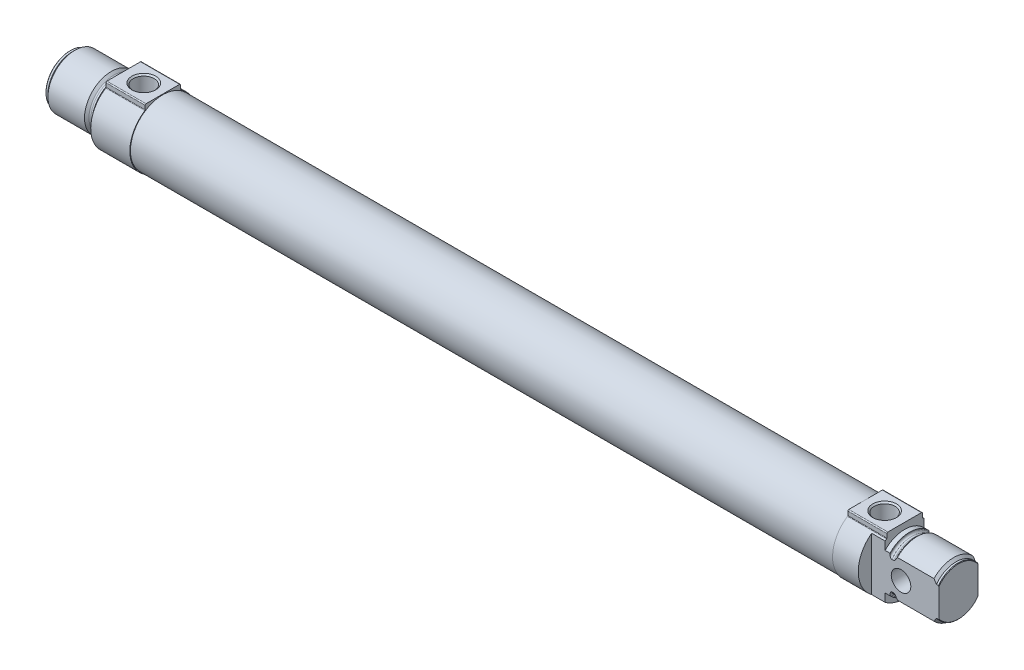
SolidWorks part; units mm, degrees
ref_plane "Ebene vorne" through (0, 0, 0) normal (0, 0, 1) x (1, 0, 0)
ref_plane "Ebene oben" through (0, 0, 0) normal (0, 1, 0) x (1, 0, 0)
ref_plane "Ebene rechts" through (0, 0, 0) normal (1, 0, 0) x (0, 0, -1)
sketch "Skizze1" plane through (0, 0, 0) normal (0, 0, 1) x (1, 0, 0)
  line L0 (0, 0) -> (0, 9.8)
  line L1 (0, 9.8) -> (0.2, 10)
  line L2 (0.2, 10) -> (1, 10)
  line L3 (1, 10) -> (2, 11)
  line L4 (2, 11) -> (16.95, 11)
  line L5 (16.95, 11) -> (17.8657, 10.0843)
  line L6 (18.4314, 9.85) -> (19.2, 9.85)
  line L7 (20, 10.65) -> (20, 11)
  line L8 (20, 11) -> (22, 11)
  line L9 (22, 11) -> (22, 0)
  line L10 (22, 0) -> (0, 0)
  line L11 (22, 0) -> (0, 0) construction
  arc A0 (17.8657, 10.0843) -> (18.4314, 9.85) centre (18.4314, 10.65) ccw
  arc A1 (19.2, 9.85) -> (20, 10.65) centre (19.2, 10.65) ccw
revolve "Rotation1" add sketch "Skizze1" angle 360 about L11 reverse direction yes
cosmetic thread "Gewindedarstellung1" parameters "D1"=15.87, "D2"=20.16
ref_plane "Ebene1" through (31.8, 0, 0) normal (1, 0, 0) x (0, 0, -1)
ref_plane "Ebene2" through (10.5, 0, 0) normal (1, 0, 0) x (0, 0, -1)
ref_plane "Ebene3" through (0, -16, 0) normal (0, 1, 0) x (1, 0, 0)
ref_plane "Ebene4" through (0, 14.9, 0) normal (0, 1, 0) x (1, 0, 0)
ref_plane "Ebene5" through (0, 0, 0) normal (0, 1, 0) x (1, 0, 0)
ref_plane "Ebene6" through (0, 0, 0) normal (0, 1, 0) x (1, 0, 0)
ref_plane "Ebene7" through (22, 0, 0) normal (1, 0, 0) x (0, 0, -1)
ref_plane "Ebene8" through (22, 0, 0) normal (1, 0, 0) x (0, 0, -1)
ref_plane "Ebene9" through (35, 0, 0) normal (1, 0, 0) x (0, 0, -1)
ref_plane "Ebene10" through (26.5, 0, 0) normal (1, 0, 0) x (0, 0, -1)
ref_plane "Ebene11" through (46.5, 0, 0) normal (1, 0, 0) x (0, 0, -1)
sketch "Skizze2" plane through (22, 0, 0) normal (1, 0, 0) x (0, 0, -1)
  line L0 (7.25, 11.5515) -> (7.25, 13.1)
  line L1 (6.85, 13.5) -> (-6.85, 13.5)
  line L2 (-7.25, 13.1) -> (-7.25, 11.5515)
  arc A0 (-7.3859, 11.3004) -> (7.3859, 11.3004) centre (0, 0) ccw
  arc A1 (7.3859, 11.3004) -> (7.25, 11.5515) centre (7.55, 11.5515) cw
  arc A2 (7.25, 13.1) -> (6.85, 13.5) centre (6.85, 13.1) ccw
  arc A3 (-6.85, 13.5) -> (-7.25, 13.1) centre (-6.85, 13.1) ccw
  arc A4 (-7.25, 11.5515) -> (-7.3859, 11.3004) centre (-7.55, 11.5515) cw
extrude "Aufsatz-Linear austragen1" add sketch "Skizze2" along normal blind 16
ref_plane "Ebene12" through (34, 0, 0) normal (1, 0, 0) x (0, 0, -1)
ref_plane "Ebene13" through (0, 0, 0) normal (0, 0, 1) x (1, 0, 0)
ref_plane "Ebene14" through (0, 0, -9.1) normal (0, 0, 1) x (1, 0, 0)
ref_plane "Ebene15" through (0, 0, 0) normal (0, 1, 0) x (1, 0, 0)
ref_plane "Ebene16" through (0, 6.9, 0) normal (0, 1, 0) x (1, 0, 0)
ref_plane "Ebene17" through (0, 0, -6.6) normal (0, 0, 1) x (1, 0, 0)
ref_plane "Ebene18" through (0, 0, 0) normal (0, 1, 0) x (1, 0, 0)
ref_plane "Ebene19" through (0, 6.9, 0) normal (0, 1, 0) x (1, 0, 0)
ref_plane "Ebene20" through (0, 7.8206, -1.379) normal (0, 0.9848, -0.1736) x (1, 0, 0)
ref_plane "Ebene21" through (0, 6.3434, -1.1185) normal (0, 0.9848, -0.1736) x (1, 0, 0)
sketch "Skizze3" plane through (0, 0, 0) normal (0, 0, 1) x (1, 0, 0)
  line L0 (38, 0) -> (38, 13.25)
  line L1 (38, 13.25) -> (325.5, 13.25)
  line L2 (325.5, 13.25) -> (325.5, 0)
  line L3 (325.5, 0) -> (38, 0)
  line L4 (325.5, 0) -> (38, 0) construction
revolve "Rotation2" add sketch "Skizze3" angle 360 about L4 reverse direction yes
ref_plane "Ebene22" through (325.5, 0, 0) normal (1, 0, 0) x (0, 0, -1)
sketch "Skizze4" plane through (325.5, 0, 0) normal (1, 0, 0) x (0, 0, -1)
  line L0 (7.25, 11.5515) -> (7.25, 13.1)
  line L1 (6.85, 13.5) -> (-6.85, 13.5)
  line L2 (-7.25, 13.1) -> (-7.25, 11.5515)
  arc A0 (-7.3859, 11.3004) -> (7.3859, 11.3004) centre (0, 0) ccw
  arc A1 (7.3859, 11.3004) -> (7.25, 11.5515) centre (7.55, 11.5515) cw
  arc A2 (7.25, 13.1) -> (6.85, 13.5) centre (6.85, 13.1) ccw
  arc A3 (-6.85, 13.5) -> (-7.25, 13.1) centre (-6.85, 13.1) ccw
  arc A4 (-7.25, 11.5515) -> (-7.3859, 11.3004) centre (-7.55, 11.5515) cw
extrude "Aufsatz-Linear austragen2" add sketch "Skizze4" along normal blind 16
ref_plane "Ebene23" through (329.3, 0, 0) normal (1, 0, 0) x (0, 0, -1)
ref_plane "Ebene24" through (329.5, 0, 0) normal (1, 0, 0) x (0, 0, -1)
ref_plane "Ebene25" through (0, 0, 6.6) normal (0, 0, 1) x (1, 0, 0)
ref_plane "Ebene26" through (0, 0, 0) normal (0, 1, 0) x (1, 0, 0)
ref_plane "Ebene27" through (0, 6.9, 0) normal (0, 1, 0) x (1, 0, 0)
ref_plane "Ebene28" through (0, 7.8206, 1.379) normal (0, 0.9848, 0.1736) x (1, 0, 0)
ref_plane "Ebene29" through (0, 6.3434, 1.1185) normal (0, 0.9848, 0.1736) x (1, 0, 0)
ref_plane "Ebene30" through (389.5, 0, 0) normal (1, 0, 0) x (0, 0, -1)
sketch "Skizze5" plane through (0, 0, 0) normal (0, 0, 1) x (1, 0, 0)
  line L0 (341.5, 0) -> (341.5, 11)
  line L1 (341.5, 11) -> (343.5, 11)
  line L2 (343.5, 11) -> (343.5, 10.65)
  line L3 (344.3, 9.85) -> (345.0686, 9.85)
  line L4 (345.6343, 10.0843) -> (346.55, 11)
  line L5 (346.55, 11) -> (361.5, 11)
  line L6 (361.5, 11) -> (362.5, 10)
  line L7 (362.5, 10) -> (363.3, 10)
  line L8 (363.3, 10) -> (363.5, 9.8)
  line L9 (363.5, 9.8) -> (363.5, 0)
  line L10 (363.5, 0) -> (341.5, 0)
  line L11 (363.5, 0) -> (341.5, 0) construction
  arc A0 (343.5, 10.65) -> (344.3, 9.85) centre (344.3, 10.65) ccw
  arc A1 (345.0686, 9.85) -> (345.6343, 10.0843) centre (345.0686, 10.65) ccw
revolve "Rotation3" add sketch "Skizze5" angle 360 about L11 reverse direction yes
cosmetic thread "Gewindedarstellung2" parameters "D1"=14.87, "D2"=20.16
ref_plane "Ebene31" through (376.5, 0, 0) normal (1, 0, 0) x (0, 0, -1)
ref_plane "Ebene32" through (385, 0, 0) normal (1, 0, 0) x (0, 0, -1)
ref_plane "Ebene33" through (365, 0, 0) normal (1, 0, 0) x (0, 0, -1)
sketch "Skizze6" plane through (0, 0, 0) normal (0, 1, 0) x (1, 0, 0)
  line L0 (336, 24) -> (336, 8)
  line L1 (336, 8) -> (363.5, 8)
  line L2 (363.5, 8) -> (363.5, -8)
  line L3 (363.5, -8) -> (336, -8)
  line L4 (336, -8) -> (336, -24)
  line L5 (336, -24) -> (379.5, -24)
  line L6 (379.5, -24) -> (379.5, 24)
  line L7 (379.5, 24) -> (336, 24)
extrude "Schnitt-Linear austragen1" cut sketch "Skizze6" along normal blind 13.5 and the other way blind 13.5
ref_plane "Ebene34" through (348, 0, 0) normal (1, 0, 0) x (0, 0, -1)
hole_wizard "Bohrung1" positions "Skizze8" profile "Skizze7" legacy
sketch "Skizze8" plane through (0, 0, -8) normal (0, 0, -1) x (-1, 0, 0)
  point P0 (-348, 0)
sketch "Skizze7" plane through (348, 0, -8) normal (1, 0, 0) x (0, 1, 0)
  line L0 (0, 0) -> (0, 16)
  line L1 (0, 16) -> (4, 16)
  line L2 (4, 16) -> (4, 0)
  line L3 (4, 0) -> (0, 0)
  line L4 (0, 110) -> (0, -10) construction
  dimension "Durchmesser" = 8
  dimension "Tiefe" = 16
hole_wizard "Bohrung2" positions "Skizze10" profile "Skizze9" legacy
sketch "Skizze10" plane through (0, 13.5, 0) normal (0, 1, 0) x (1, 0, 0)
  point P0 (30.2, 0)
sketch "Skizze9" plane through (30.2, 13.5, 0) normal (1, 0, 0) x (0, 0, 1)
  line L0 (0, 0) -> (0, 13.5)
  line L1 (0, 13.5) -> (4.283, 13.5)
  line L2 (4.283, 13.5) -> (4.283, 0.581)
  line L3 (4.283, 0.581) -> (4.864, 0)
  line L4 (4.864, 0) -> (0, 0)
  line L5 (0, -6.4453) -> (0, 115.525) construction
  line L6 (-4.283, 0.581) -> (-4.864, 0) construction
  dimension "Durchmesser" = 8.566
  dimension "Tiefe" = 13.5
  dimension "Senkwinkel1" = 90
  dimension "Senkdurchmesser3" = 9.728
cosmetic thread "Gewindedarstellung3" parameters "D1"=8.5, "D2"=9.728
hole_wizard "Bohrung3" positions "Skizze12" profile "Skizze11" legacy
sketch "Skizze12" plane through (0, 13.5, 0) normal (0, 1, 0) x (1, 0, 0)
  point P0 (333.3, 0)
sketch "Skizze11" plane through (333.3, 13.5, 0) normal (1, 0, 0) x (0, 0, 1)
  line L0 (0, 0) -> (0, 18.4728)
  line L1 (0, 18.4728) -> (4.283, 16)
  line L2 (4.283, 16) -> (4.283, 0.581)
  line L3 (4.283, 0.581) -> (4.864, 0)
  line L4 (4.864, 0) -> (0, 0)
  line L5 (0, -14.3089) -> (0, 102.4216) construction
  line L6 (0, 18.4728) -> (-4.283, 16) construction
  line L7 (-4.283, 0.581) -> (-4.864, 0) construction
  dimension "Durchmesser" = 8.566
  dimension "Tiefe" = 16
  dimension "Senkdurchmesser1" = 9.728
  dimension "Senkwinkel1" = 90
  dimension "Spitzenwinkel" = 120
cosmetic thread "Gewindedarstellung4" parameters "D1"=8, "D2"=9.728
sketch "Skizze13" plane through (0, 0, 0) normal (0, 0, 1) x (1, 0, 0)
  line L0 (-6, 0) -> (-6, 5)
  line L1 (-6, 5) -> (52.6, 5)
  line L2 (52.6, 5) -> (52.6, 12.5)
  line L3 (52.6, 12.5) -> (308.85, 12.5)
  line L4 (308.85, 12.5) -> (308.85, 0)
  line L5 (308.85, 0) -> (-6, 0)
  line L6 (308.85, 0) -> (-6, 0) construction
revolve "Schnitt-Rotation1" cut sketch "Skizze13" angle 360 about L6 reverse direction yes
ref_plane "Ebene35" through (-6, 0, 0) normal (1, 0, 0) x (0, 0, -1)
ref_plane "Ebene36" through (0, 13.5, 0) normal (0, 1, 0) x (1, 0, 0)
ref_plane "Ebene37" through (8.5, 0, 0) normal (1, 0, 0) x (0, 0, -1)
ref_plane "Ebene38" through (0, 0, 0) normal (1, 0, 0) x (0, 0, -1)
ref_plane "Ebene39" through (22, 0, 0) normal (1, 0, 0) x (0, 0, -1)
ref_plane "Ebene40" through (341.5, 0, 0) normal (1, 0, 0) x (0, 0, -1)
ref_plane "Ebene41" through (22, 0, 0) normal (1, 0, 0) x (0, 0, -1)
ref_plane "Ebene42" through (0, 13.5, 0) normal (0, 1, 0) x (1, 0, 0)
ref_plane "Ebene43" through (47.5, 0, 0) normal (1, 0, 0) x (0, 0, -1)
ref_plane "Ebene44" through (316, 0, 0) normal (1, 0, 0) x (0, 0, -1)
ref_plane "Ebene45" through (0, 0, 0) normal (0, 0, 1) x (1, 0, 0)
ref_plane "Ebene46" through (22, 0, 0) normal (1, 0, 0) x (0, 0, -1)
ref_plane "Ebene47" through (0, 13.5, 0) normal (0, 1, 0) x (1, 0, 0)
ref_plane "FDT_FRONT XY" through (22, 0, 0) normal (1, 0, 0) x (0, 0, -1)
ref_plane "FDT_FRONT XZ" through (0, 0, 0) normal (0, -1, 0) x (-1, 0, 0)
ref_plane "FDT_FRONT YZ" through (0, 0, 0) normal (0, 0, -1) x (-1, 0, 0)
ref_axis "FDT_FRONT X" through (22, 0, 80.9) along (0, 0, -1)
ref_axis "FDT_FRONT Y" through (22, -50, 0) along (0, 1, 0)
ref_axis "FDT_FRONT Z" through (80.9, 0, 0) along (-1, 0, 0)
sketch3d "FDT_FRONT"
  point P0 (22, 0, 0)
ref_plane "FDT_QSFRONT XY" through (0, 13.5, 0) normal (0, 1, 0) x (1, 0, 0)
ref_plane "FDT_QSFRONT XZ" through (30.2, 0, 0) normal (-1, 0, 0) x (0, 0, 1)
ref_plane "FDT_QSFRONT YZ" through (0, 0, 0) normal (0, 0, 1) x (1, 0, 0)
ref_axis "FDT_QSFRONT X" through (30.2, 13.5, -50) along (0, 0, 1)
ref_axis "FDT_QSFRONT Y" through (-80.9, 13.5, 0) along (1, 0, 0)
ref_axis "FDT_QSFRONT Z" through (30.2, 50, 0) along (0, -1, 0)
sketch3d "FDT_QSFRONT"
  point P0 (30.2, 13.5, 0)
ref_plane "FDT_QSREAR XY" through (0, 13.5, 0) normal (0, 1, 0) x (1, 0, 0)
ref_plane "FDT_QSREAR XZ" through (333.3, 0, 0) normal (-1, 0, 0) x (0, 0, 1)
ref_plane "FDT_QSREAR YZ" through (0, 0, 0) normal (0, 0, 1) x (1, 0, 0)
ref_axis "FDT_QSREAR X" through (333.3, 13.5, -50) along (0, 0, 1)
ref_axis "FDT_QSREAR Y" through (-80.9, 13.5, 0) along (1, 0, 0)
ref_axis "FDT_QSREAR Z" through (333.3, 50, 0) along (0, -1, 0)
sketch3d "FDT_QSREAR"
  point P0 (333.3, 13.5, 0)
ref_plane "FDT_REAR XY" through (341.5, 0, 0) normal (-1, 0, 0) x (0, 0, 1)
ref_plane "FDT_REAR XZ" through (0, 0, 0) normal (0, 1, 0) x (1, 0, 0)
ref_plane "FDT_REAR YZ" through (0, 0, 0) normal (0, 0, -1) x (-1, 0, 0)
ref_axis "FDT_REAR X" through (341.5, 0, 80.9) along (0, 0, -1)
ref_axis "FDT_REAR Y" through (341.5, 50, 0) along (0, -1, 0)
ref_axis "FDT_REAR Z" through (-80.9, 0, 0) along (1, 0, 0)
sketch3d "FDT_REAR"
  point P0 (341.5, 0, 0)
ref_plane "FDT_SMBR1 XY" through (47.5, 0, 0) normal (-1, 0, 0) x (0, 0, 1)
ref_plane "FDT_SMBR1 XZ" through (0, 0, 0) normal (0, -1, 0) x (-1, 0, 0)
ref_plane "FDT_SMBR1 YZ" through (0, 0, 0) normal (0, 0, 1) x (1, 0, 0)
ref_axis "FDT_SMBR1 X" through (47.5, 0, -80.9) along (0, 0, 1)
ref_axis "FDT_SMBR1 Y" through (47.5, -50, 0) along (0, 1, 0)
ref_axis "FDT_SMBR1 Z" through (-80.9, 0, 0) along (1, 0, 0)
sketch3d "FDT_SMBR1"
  point P0 (47.5, 0, 0)
ref_plane "FDT_SMBR2 XY" through (316, 0, 0) normal (-1, 0, 0) x (0, 0, 1)
ref_plane "FDT_SMBR2 XZ" through (0, 0, 0) normal (0, -1, 0) x (-1, 0, 0)
ref_plane "FDT_SMBR2 YZ" through (0, 0, 0) normal (0, 0, 1) x (1, 0, 0)
ref_axis "FDT_SMBR2 X" through (316, 0, -80.9) along (0, 0, 1)
ref_axis "FDT_SMBR2 Y" through (316, -50, 0) along (0, 1, 0)
ref_axis "FDT_SMBR2 Z" through (-80.9, 0, 0) along (1, 0, 0)
sketch3d "FDT_SMBR2"
  point P0 (316, 0, 0)
ref_plane "FDT_SWIVELAXIS XY" through (0, 0, 0) normal (0, 0, 1) x (1, 0, 0)
ref_plane "FDT_SWIVELAXIS XZ" through (0, 0, 0) normal (0, -1, 0) x (-1, 0, 0)
ref_plane "FDT_SWIVELAXIS YZ" through (348, 0, 0) normal (1, 0, 0) x (0, 0, -1)
ref_axis "FDT_SWIVELAXIS X" through (-80.9, 0, 0) along (1, 0, 0)
ref_axis "FDT_SWIVELAXIS Y" through (348, -50, 0) along (0, 1, 0)
ref_axis "FDT_SWIVELAXIS Z" through (348, 0, 80.9) along (0, 0, -1)
sketch3d "FDT_SWIVELAXIS"
  point P0 (348, 0, 0)
ref_plane "NUT XY" through (8.5, 0, 0) normal (1, 0, 0) x (0, 0, -1)
ref_plane "NUT XZ" through (0, 0, 0) normal (0, -1, 0) x (-1, 0, 0)
ref_plane "NUT YZ" through (0, 0, 0) normal (0, 0, -1) x (-1, 0, 0)
ref_axis "NUT X" through (8.5, 0, 80.9) along (0, 0, -1)
ref_axis "NUT Y" through (8.5, -50, 0) along (0, 1, 0)
ref_axis "NUT Z" through (80.9, 0, 0) along (-1, 0, 0)
sketch3d "NUT"
  point P0 (8.5, 0, 0)
ref_plane "ZR XY" through (0, 0, 0) normal (1, 0, 0) x (0, 0, -1)
ref_plane "ZR XZ" through (0, 0, 0) normal (0, -1, 0) x (-1, 0, 0)
ref_plane "ZR YZ" through (0, 0, 0) normal (0, 0, -1) x (-1, 0, 0)
ref_axis "ZR X" through (0, 0, 80.9) along (0, 0, -1)
ref_axis "ZR Y" through (0, -50, 0) along (0, 1, 0)
ref_axis "ZR Z" through (80.9, 0, 0) along (-1, 0, 0)
sketch3d "ZR"
  point P0 (0, 0, 0)
ref_plane "ZYL XY" through (22, 0, 0) normal (1, 0, 0) x (0, 0, -1)
ref_plane "ZYL XZ" through (0, 0, 0) normal (0, -1, 0) x (-1, 0, 0)
ref_plane "ZYL YZ" through (0, 0, 0) normal (0, 0, -1) x (-1, 0, 0)
ref_axis "ZYL X" through (22, 0, 80.9) along (0, 0, -1)
ref_axis "ZYL Y" through (22, -50, 0) along (0, 1, 0)
ref_axis "ZYL Z" through (80.9, 0, 0) along (-1, 0, 0)
sketch3d "ZYL"
  point P0 (22, 0, 0)
